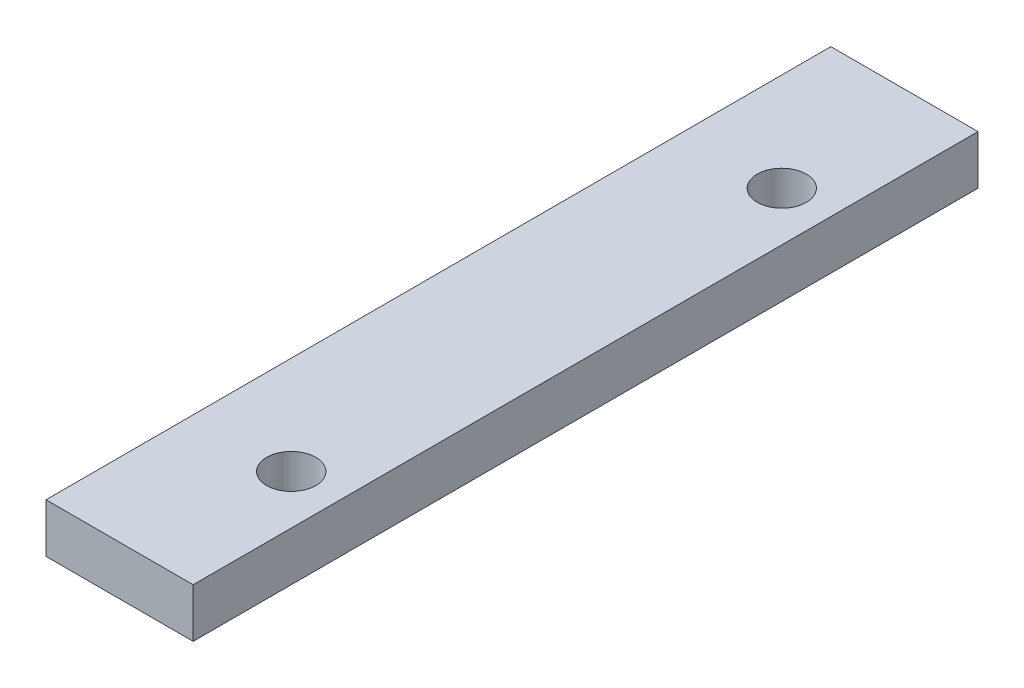
SolidWorks part; units mm, degrees
ref_plane "Front Plane" through (0, 0, 0) normal (0, 0, 1) x (1, 0, 0)
ref_plane "Top Plane" through (0, 0, 0) normal (0, 1, 0) x (1, 0, 0)
ref_plane "Right Plane" through (0, 0, 0) normal (1, 0, 0) x (0, 0, -1)
sketch "Sketch1" plane through (0, 0, 0) normal (0, 1, 0) x (1, 0, 0)
  line L1 (9.525, -50.8) -> (-9.525, -50.8)
  line L2 (9.525, -50.8) -> (9.525, 50.8)
  line L3 (9.525, 50.8) -> (-9.525, 50.8)
  line L4 (-9.525, -50.8) -> (-9.525, 50.8)
  line L5 (9.525, -50.8) -> (-9.525, 50.8) construction
  line L6 (9.525, 50.8) -> (-9.525, -50.8) construction
  point P0 (0, 0)
  dimension "D1" = 101.6
  dimension "D2" = 19.05
extrude "Boss-Extrude1" add sketch "Sketch1" along normal mid plane 6.35
hole_wizard "1/4 (0.25) Diameter Hole1" positions "Sketch2" profile "Sketch3" hole size "1/4" standard "ANSI Inch" end condition through all
sketch "Sketch2" plane through (0, 3.175, 0) normal (0, 1, 0) x (1, 0, 0)
  line L0 (-9.525, -50.8) -> (9.525, -50.8) construction
  line L1 (9.525, 50.8) -> (-9.525, 50.8) construction
  line L2 (9.525, -50.8) -> (9.525, 50.8) construction
  point P0 (3.175, -31.75)
  point P2 (3.175, 31.75)
  dimension "D1" = 19.05
  dimension "D2" = 19.05
  dimension "D3" = 6.35
  dimension "D4" = 6.35
sketch "Sketch3" plane through (3.175, 3.175, 31.75) normal (1, 0, 0) x (0, 0, 1)
  line L0 (0, 0) -> (0, 6.35)
  line L1 (0, 6.35) -> (3.175, 6.35)
  line L2 (3.175, 6.35) -> (3.175, 0)
  line L5 (3.175, 0) -> (0, 0)
  line L11 (0, -6.35) -> (0, 107.95) construction
  dimension "Thru Hole Dia." = 6.35
  dimension "Thru Hole Depth" = 6.35
